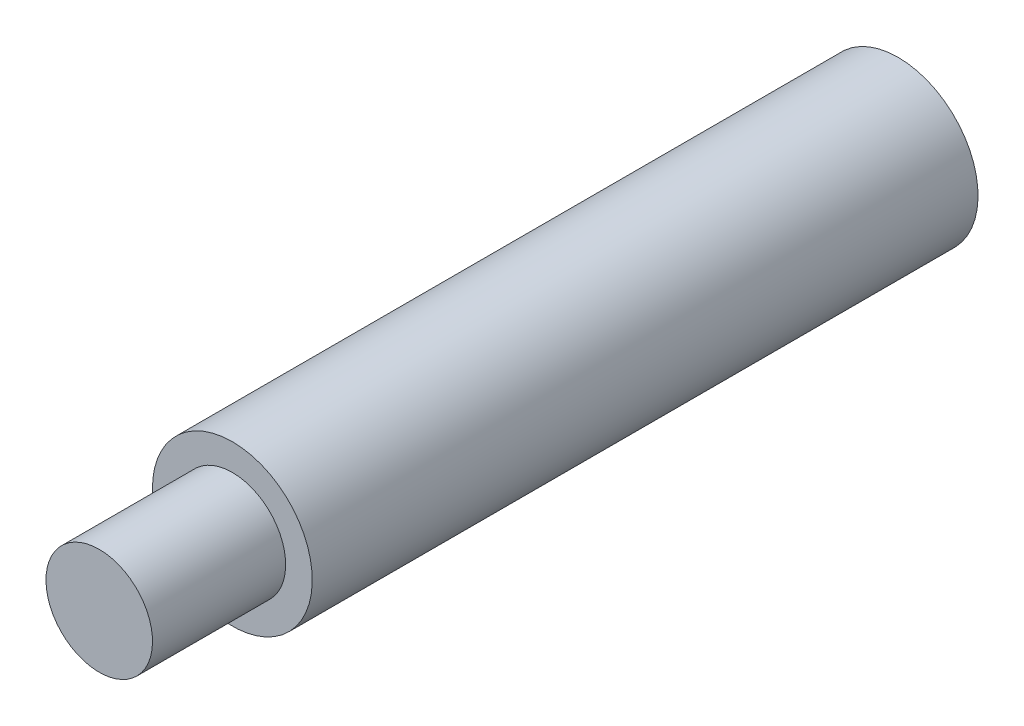
SolidWorks part; units mm, degrees
material "Plain Carbon Steel"
ref_plane "Front Plane" through (0, 0, 0) normal (0, 0, 1) x (1, 0, 0)
ref_plane "Top Plane" through (0, 0, 0) normal (0, 1, 0) x (1, 0, 0)
ref_plane "Right Plane" through (0, 0, 0) normal (1, 0, 0) x (0, 0, -1)
sketch "Sketch1" plane through (0, 0, 0) normal (1, 0, 0) x (0, 0, -1)
  line L0 (-10, 0) -> (-10, 4)
  line L1 (-10, 4) -> (0, 4)
  line L2 (0, 4) -> (0, 6)
  line L3 (0, 6) -> (50, 6)
  line L4 (50, 6) -> (50, 4)
  line L5 (50, 4) -> (40, 4)
  line L6 (40, 4) -> (40, 0)
  line L7 (40, 0) -> (-10, 0)
  dimension "D1" = 50
  dimension "D2" = 6
  dimension "D3" = 4
  dimension "D4" = 10
revolve "Revolve1" add sketch "Sketch1" angle 360 about L7
